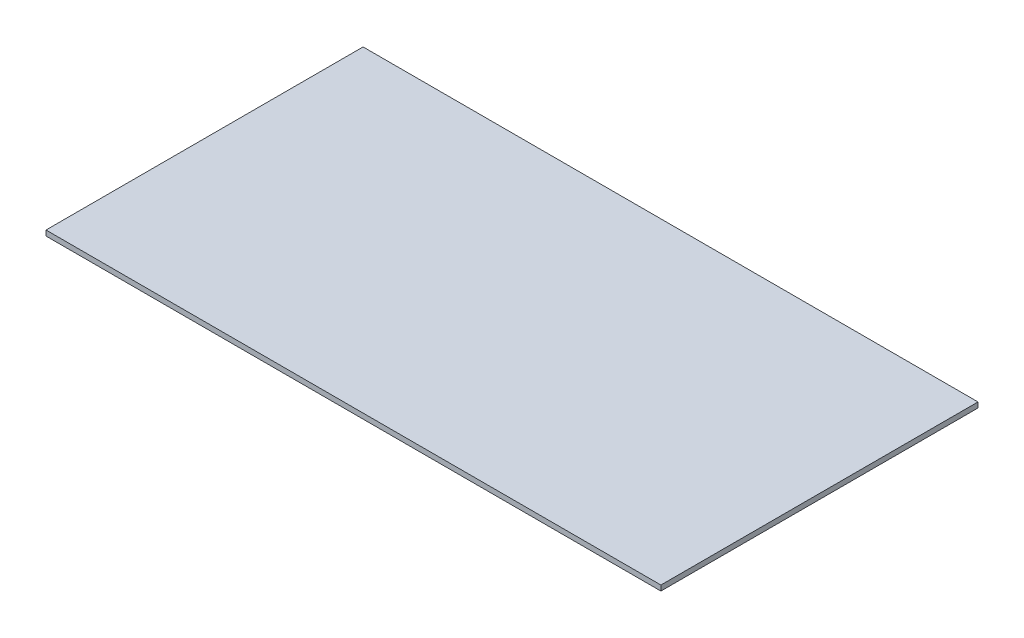
SolidWorks part; units mm, degrees
ref_plane "Front Plane" through (0, 0, 0) normal (0, 0, 1) x (1, 0, 0)
ref_plane "Top Plane" through (0, 0, 0) normal (0, 1, 0) x (1, 0, 0)
ref_plane "Right Plane" through (0, 0, 0) normal (1, 0, 0) x (0, 0, -1)
sketch "Sketch1" plane through (0, 0, 0) normal (0, 1, 0) x (1, 0, 0)
  line L1 (-30.5271, 0) -> (320.459, 0)
  line L2 (-30.5271, 0) -> (-30.5271, 181)
  line L3 (-30.5271, 181) -> (320.459, 181)
  line L4 (320.459, 0) -> (320.459, 181)
  dimension "D1" = 181
extrude "Boss-Extrude1" add sketch "Sketch1" along normal blind 3
